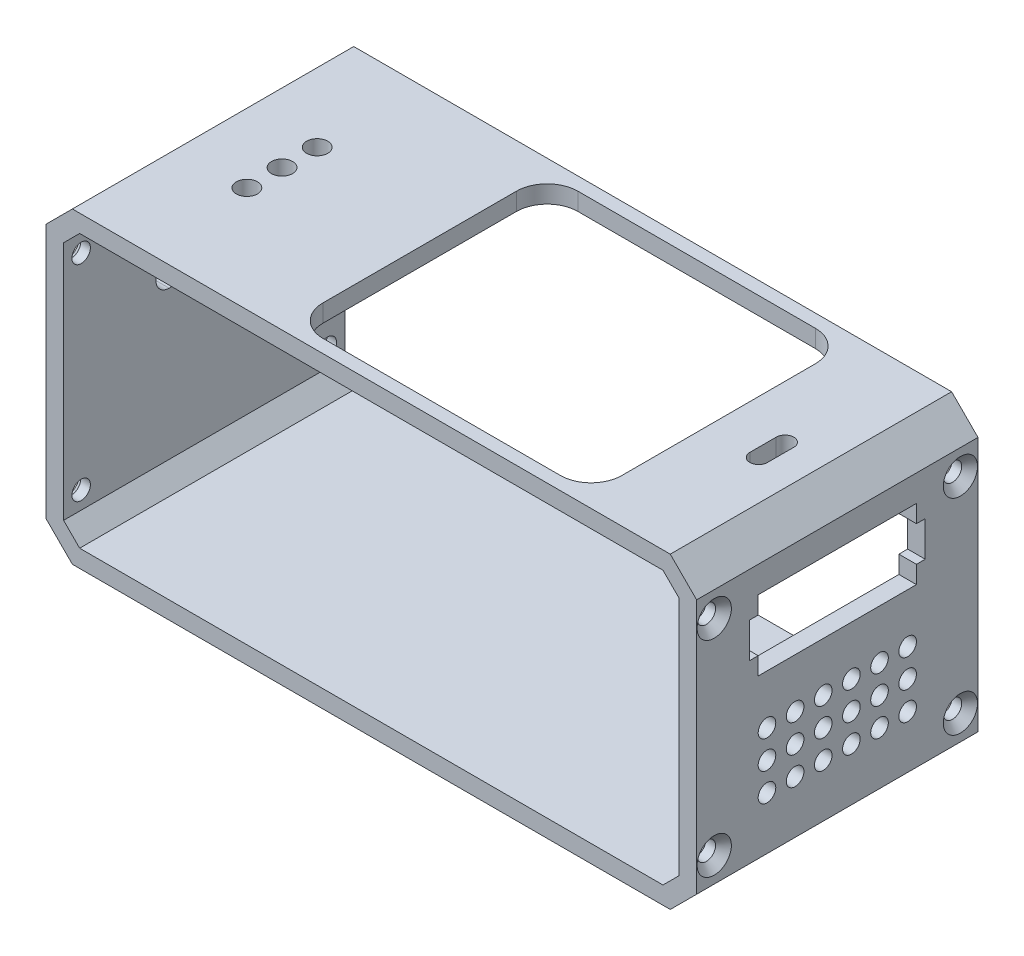
SolidWorks part; units mm, degrees
ref_plane "前视基准面" through (0, 0, 0) normal (0, 0, 1) x (1, 0, 0)
ref_plane "上视基准面" through (0, 0, 0) normal (0, 1, 0) x (1, 0, 0)
ref_plane "右视基准面" through (0, 0, 0) normal (1, 0, 0) x (0, 0, -1)
other "Configuration Table"
sketch "草图1" plane through (0, 0, 0) normal (0, 1, 0) x (1, 0, 0)
  line L0 (-32.2834, 0.435) -> (-71.9856, 0.435) construction
  line L1 (-36.9634, 16.435) -> (37.0366, 16.435)
  line L2 (-36.9634, 16.435) -> (-36.9634, -15.565)
  line L3 (-36.9634, -15.565) -> (37.0366, -15.565)
  line L4 (37.0366, 16.435) -> (37.0366, -15.565)
  line L6 (-32.2834, 11.935) -> (-32.2834, -11.065) construction
  point P6 (-36.9634, 0.435)
  point P9 (-32.2834, 0.435)
  dimension "D1" = 32
  dimension "D2" = 74
extrude "凸台-拉伸1" add sketch "草图1" along normal blind 35
chamfer "倒角1" distance 3 angle 45 4 edges at (37.0366, 0, -0.435) (-36.9634, 0, -0.435) (-36.9634, 35, -0.435) (37.0366, 35, -0.435)
sketch "草图2" plane through (0, 0, 15.565) normal (0, 0, 1) x (1, 0, 0)
  line L8 (-33.135, 2) -> (33.2082, 2)
  line L9 (35.0366, 3.8284) -> (35.0366, 31.1716)
  line L10 (33.2082, 33) -> (-33.135, 33)
  line L11 (-34.9634, 31.1716) -> (-34.9634, 3.8284)
  line L12 (-33.135, 2) -> (33.2082, 2)
  line L13 (35.0366, 3.8284) -> (35.0366, 31.1716)
  line L14 (33.2082, 33) -> (-33.135, 33)
  line L15 (-34.9634, 31.1716) -> (-34.9634, 3.8284)
  line L16 (33.2082, 2) -> (35.0366, 3.8284)
  line L17 (33.2082, 2) -> (35.0366, 3.8284)
  line L18 (35.0366, 31.1716) -> (33.2082, 33)
  line L19 (35.0366, 31.1716) -> (33.2082, 33)
  line L20 (-33.135, 33) -> (-34.9634, 31.1716)
  line L21 (-33.135, 33) -> (-34.9634, 31.1716)
  line L22 (-34.9634, 3.8284) -> (-33.135, 2)
  line L23 (-34.9634, 3.8284) -> (-33.135, 2)
  dimension "D1" = 2
extrude "切除-拉伸1" cut sketch "草图2" against normal through all
sketch "草图4" plane through (0, 35, 0) normal (0, 1, 0) x (1, 0, 0)
  line L0 (34.0366, 16.435) -> (-33.9634, 16.435) construction
  line L1 (-6.9634, 14.935) -> (20.0366, 14.935)
  line L2 (-10.4634, 11.435) -> (-10.4634, -10.565)
  line L3 (-6.9634, -14.065) -> (20.0366, -14.065)
  line L4 (23.5366, 11.435) -> (23.5366, -10.565)
  line L5 (-33.9634, -15.565) -> (34.0366, -15.565) construction
  line L7 (37.0366, 16.435) -> (37.0366, -15.565) construction
  arc A0 (20.0366, -14.065) -> (23.5366, -10.565) centre (20.0366, -10.565) ccw
  arc A1 (20.0366, 14.935) -> (23.5366, 11.435) centre (20.0366, 11.435) cw
  arc A2 (-10.4634, -10.565) -> (-6.9634, -14.065) centre (-6.9634, -10.565) ccw
  arc A3 (-6.9634, 14.935) -> (-10.4634, 11.435) centre (-6.9634, 11.435) ccw
  point P4 (23.2166, 14.9981)
  point P5 (23.6689, 14.9981)
  point P14 (23.5366, -14.065)
  point P17 (23.5366, 14.935)
  point P22 (-10.4634, 14.935)
  dimension "D5" = 3.5
  dimension "D1" = 34
  dimension "D2" = 1.5
  dimension "D3" = 1.5
  dimension "D4" = 13.5
extrude "切除-拉伸2" cut sketch "草图4" against normal up to next
sketch "草图5" plane through (0, 35, 0) normal (0, 1, 0) x (1, 0, 0)
  line L0 (-36.9634, 0.435) -> (-43.9993, 0.435) construction
  circle A0 centre (-26.1174, 0.435) radius 1.2
  circle A1 centre (-26.1174, 4.435) radius 1.2
  circle A2 centre (-26.1174, -3.565) radius 1.2
  point P8 (0, 0)
  point P9 (0, 0)
  dimension "D3" = 2.4
  dimension "D1" = 4
  dimension "D2" = 4
extrude "切除-拉伸3" cut sketch "草图5" against normal up to next
sketch "草图6" plane through (37.0366, 0, 0) normal (1, 0, 0) x (0, 0, -1)
  circle A0 centre (-13.565, 29.1716) radius 1.05
  circle A1 centre (-13.565, 5.8284) radius 1.05
  circle A2 centre (14.435, 5.8284) radius 1.05
  circle A3 centre (14.435, 29.1716) radius 1.05
  dimension "D1" = 2.1
extrude "切除-拉伸4" cut sketch "草图6" against normal through all
chamfer "倒角2" distance 0.9 angle 45 8 edges at (37.0366, 29.1716, -15.485) (37.0366, 5.8284, -15.485) (37.0366, 29.1716, 12.515) (37.0366, 5.8284, 12.515) (-36.9634, 5.8284, -15.485) (-36.9634, 29.1716, -15.485) (-36.9634, 5.8284, 12.515) (-36.9634, 29.1716, 12.515)
sketch "草图7" plane through (0, 35, 0) normal (0, 1, 0) x (1, 0, 0)
  line L0 (34.0366, 0.435) -> (47.8552, 0.435) construction
  line L2 (29.5366, 1.9891) -> (29.5366, -1.0109) construction
  line L3 (30.5366, 1.9891) -> (30.5366, -1.0109)
  line L4 (28.5366, 1.9891) -> (28.5366, -1.0109)
  line L5 (37.0366, 16.435) -> (37.0366, -15.565) construction
  arc A0 (30.5366, 1.9891) -> (28.5366, 1.9891) centre (29.5366, 1.9891) ccw
  arc A1 (28.5366, -1.0109) -> (30.5366, -1.0109) centre (29.5366, -1.0109) ccw
  point P3 (29.5366, 0.4891)
  dimension "D3" = 1
  dimension "D1" = 7.5
  dimension "D2" = 3
extrude "切除-拉伸5" cut sketch "草图7" against normal up to next
sketch "草图8" plane through (-36.9634, 0, 0) normal (-1, 0, 0) x (0, 0, 1)
  line L0 (-2.435, 11.4156) -> (-2.435, -8.1835) construction
  line L1 (-8.435, 22.2) -> (3.565, 22.2) construction
  line L2 (-8.435, 23.7) -> (3.565, 23.7)
  line L3 (-8.435, 20.7) -> (3.565, 20.7)
  line L4 (-16.435, 32) -> (-16.435, 3) construction
  line L5 (-16.435, 35) -> (15.565, 35) construction
  arc A0 (-8.435, 23.7) -> (-8.435, 20.7) centre (-8.435, 22.2) ccw
  arc A1 (3.565, 20.7) -> (3.565, 23.7) centre (3.565, 22.2) ccw
  point P3 (-2.435, 22.2)
  point P9 (0, 0)
  dimension "D4" = 1.5
  dimension "D1" = 14
  dimension "D2" = 12
  dimension "D3" = 12.8
extrude "切除-拉伸6" cut sketch "草图8" against normal up to next
sketch "草图9" plane through (-36.9634, 0, 0) normal (-1, 0, 0) x (0, 0, 1)
  line L0 (-16.435, 32) -> (-16.435, 3) construction
  line L1 (-7.435, 17) -> (-3.435, 17)
  line L2 (-7.435, 17) -> (-7.435, 15)
  line L3 (-7.435, 15) -> (-3.435, 15)
  line L4 (-3.435, 17) -> (-3.435, 15)
  line L5 (-16.435, 35) -> (15.565, 35) construction
  dimension "D1" = 9
  dimension "D2" = 2
  dimension "D3" = 18
  dimension "D4" = 4
extrude "切除-拉伸7" cut sketch "草图9" against normal up to next
fillet "圆角1" radius 1 4 edges at (-35.9634, 15, -3.435) (-35.9634, 17, -3.435) (-35.9634, 17, -7.435) (-35.9634, 15, -7.435)
sketch "草图10" plane through (-36.9634, 0, 0) normal (-1, 0, 0) x (0, 0, 1)
  line L0 (-16.435, 35) -> (15.565, 35) construction
  line L1 (-16.435, 32) -> (-16.435, 3) construction
  circle A0 centre (-8.935, 28.6) radius 1
  circle A1 centre (-5.735, 28.6) radius 1
  circle A2 centre (-2.535, 28.6) radius 1
  circle A3 centre (0.665, 28.6) radius 1
  circle A4 centre (3.865, 28.6) radius 1
  circle A5 centre (-5.735, 25.4) radius 1
  circle A6 centre (-2.535, 25.4) radius 1
  circle A7 centre (0.665, 25.4) radius 1
  circle A8 centre (3.865, 25.4) radius 1
  circle A9 centre (-8.935, 25.4) radius 1
  dimension "D3" = 2
  dimension "D1" = 6.4
  dimension "D2" = 7.5
  dimension "D4" = 5
  dimension "D5" = 2
extrude "切除-拉伸8" cut sketch "草图10" against normal up to next
sketch "草图11" plane through (37.0366, 0, 0) normal (1, 0, 0) x (0, 0, -1)
  line L0 (-15.565, 3) -> (16.435, 3) construction
  line L1 (-8.565, 29) -> (9.435, 29)
  line L3 (-8.565, 21) -> (9.435, 21)
  line L5 (-15.565, 35) -> (16.435, 35) construction
  line L6 (-8.565, 29) -> (-8.565, 27)
  line L7 (-8.565, 24) -> (-8.565, 30) construction
  line L8 (-8.565, 27) -> (-9.565, 27)
  line L9 (-9.565, 27) -> (-9.565, 23)
  line L10 (-9.565, 23) -> (-8.565, 23)
  line L11 (-8.565, 23) -> (-8.565, 21)
  line L12 (9.435, 29) -> (9.435, 27)
  line L13 (9.435, 27) -> (10.435, 27)
  line L14 (10.435, 27) -> (10.435, 23)
  line L15 (10.435, 23) -> (9.435, 23)
  line L16 (9.435, 23) -> (9.435, 21)
  point P6 (0.435, 3)
  point P7 (0.435, 29)
  point P20 (0, 0)
  point P21 (0, 0)
  point P22 (0, 0)
  dimension "D1" = 18
  dimension "D2" = 8
  dimension "D3" = 6
  dimension "D4" = 1
  dimension "D5" = 2
  dimension "D6" = 4
extrude "切除-拉伸9" cut sketch "草图11" against normal up to next
sketch "草图12" plane through (37.0366, 0, 0) normal (1, 0, 0) x (0, 0, -1)
  line L0 (16.435, 0) -> (-15.565, 0) construction
  line L1 (-15.565, 0) -> (-15.565, 3) construction
  line L2 (-8.565, 28) -> (-8.565, 12.1375) construction
  circle A0 centre (-7.565, 9) radius 1
  circle A1 centre (-4.365, 9) radius 1
  circle A2 centre (-1.165, 9) radius 1
  circle A3 centre (2.035, 9) radius 1
  circle A4 centre (5.235, 9) radius 1
  circle A5 centre (8.435, 9) radius 1
  circle A6 centre (-4.365, 12.2) radius 1
  circle A7 centre (-1.165, 12.2) radius 1
  circle A8 centre (2.035, 12.2) radius 1
  circle A9 centre (5.235, 12.2) radius 1
  circle A10 centre (8.435, 12.2) radius 1
  circle A11 centre (-4.365, 15.4) radius 1
  circle A12 centre (-1.165, 15.4) radius 1
  circle A13 centre (2.035, 15.4) radius 1
  circle A14 centre (5.235, 15.4) radius 1
  circle A15 centre (8.435, 15.4) radius 1
  circle A16 centre (-7.565, 12.2) radius 1
  circle A17 centre (-7.565, 15.4) radius 1
  dimension "D1" = 2
  dimension "D2" = 9
  dimension "D3" = 8
extrude "切除-拉伸10" cut sketch "草图12" against normal up to next
